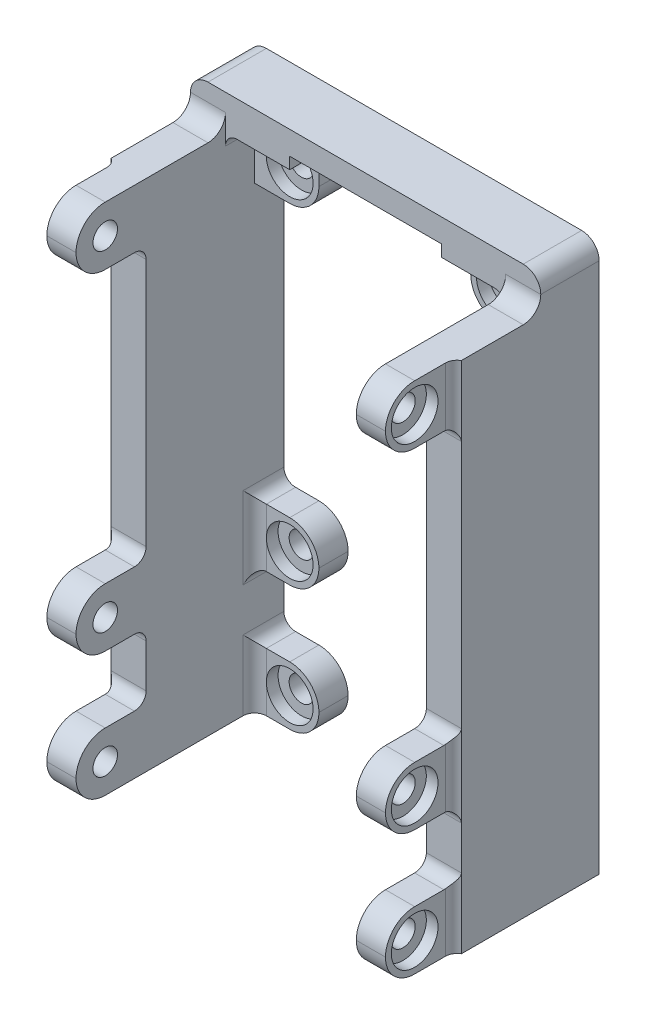
SolidWorks part; units mm, degrees
material "Esun Hard Tough Resin"
ref_plane "Front Plane" through (0, 0, 0) normal (0, 0, 1) x (1, 0, 0)
ref_plane "Top Plane" through (0, 0, 0) normal (0, 1, 0) x (1, 0, 0)
ref_plane "Right Plane" through (0, 0, 0) normal (1, 0, 0) x (0, 0, -1)
sketch "Sketch1" plane through (0, 0, 0) normal (0, 0, 1) x (1, 0, 0)
  line L1 (-15, -22) -> (15, -22)
  line L2 (-15, -22) -> (-15, 22)
  line L3 (-15, 22) -> (15, 22)
  line L4 (15, -22) -> (15, 22)
  line L5 (-15, -22) -> (15, 22) construction
  line L6 (-15, 22) -> (15, -22) construction
  line L7 (-12, 22) -> (12, 22)
  line L8 (-12, 22) -> (-12, -22)
  line L9 (-12, -22) -> (12, -22)
  line L10 (12, 22) -> (12, -22)
  line L11 (-12, 22) -> (12, -22) construction
  line L12 (-12, -22) -> (12, 22) construction
  point P0 (0, 0)
  point P6 (0, 0)
  dimension "D1" = 30
  dimension "D2" = 44
  dimension "D3" = 24
extrude "Boss-Extrude1" add sketch "Sketch1" along normal blind 11.8 contours L8 L3 L2 L1 | L3 L10 L1 L4
sketch "Sketch2" plane through (0, 0, 0) normal (0, 0, -1) x (-1, 0, 0)
  line L1 (-15, 22) -> (15, 22)
  line L2 (-15, 22) -> (-15, 25)
  line L3 (-15, 25) -> (15, 25)
  line L4 (15, 22) -> (15, 25)
  dimension "D1" = 3
extrude "Boss-Extrude2" add sketch "Sketch2" against normal blind 5
sketch "Sketch3" plane through (0, 0, 11.8) normal (0, 0, 1) x (1, 0, 0)
  line L0 (-12, 22) -> (-12, -22) construction
  line L1 (-12, 22) -> (-14.5, 22)
  line L2 (-12, 22) -> (-12, 17)
  line L3 (-12, 17) -> (-14.5, 17)
  line L4 (-14.5, 22) -> (-14.5, 17)
  line L5 (-12, -6.3) -> (-14.5, -6.3)
  line L6 (-12, -6.3) -> (-12, -11.3)
  line L7 (-12, -11.3) -> (-14.5, -11.3)
  line L8 (-14.5, -6.3) -> (-14.5, -11.3)
  line L9 (0, -1000) -> (0, 49000) construction
  line L10 (-12, -17) -> (-14.5, -17)
  line L11 (-12, -17) -> (-12, -22)
  line L12 (-12, -22) -> (-14.5, -22)
  line L13 (-14.5, -17) -> (-14.5, -22)
  line L14 (12, -22) -> (14.5, -22)
  line L15 (14.5, -17) -> (14.5, -22)
  line L16 (12, -17) -> (14.5, -17)
  line L17 (12, -17) -> (12, -22)
  line L18 (12, -11.3) -> (14.5, -11.3)
  line L19 (14.5, -6.3) -> (14.5, -11.3)
  line L20 (12, -6.3) -> (14.5, -6.3)
  line L21 (12, -6.3) -> (12, -11.3)
  line L22 (12, 17) -> (14.5, 17)
  line L23 (14.5, 22) -> (14.5, 17)
  line L24 (12, 22) -> (14.5, 22)
  line L25 (12, 22) -> (12, 17)
  point P15 (-14.5, 19.5)
  point P16 (-14.5, -8.8)
  point P17 (-14.5, -19.5)
  dimension "D1" = 2.5
  dimension "D2" = 2.5
  dimension "D3" = 2.5
  dimension "D4" = 5
  dimension "D5" = 5
  dimension "D6" = 5
  dimension "D7" = 28.3
  dimension "D8" = 10.7
extrude "Boss-Extrude3" add sketch "Sketch3" along normal blind 6
sketch "Sketch4" plane through (-14.5, 0, 0) normal (-1, 0, 0) x (0, 0, 1)
  line L0 (17.8, 22) -> (17.8, 17) construction
  line L2 (17.8, -6.3) -> (17.8, -11.3) construction
  line L4 (17.8, -17) -> (17.8, -22) construction
  circle A0 centre (15.3, 19.5) radius 1.05
  circle A1 centre (15.3, -8.8) radius 1.05
  circle A2 centre (15.3, -19.5) radius 1.05
  point P5 (17.8, 19.5)
  point P12 (17.8, -8.8)
  point P20 (17.8, -19.5)
  dimension "D1" = 2.1
  dimension "D2" = 2.1
  dimension "D3" = 2.1
  dimension "D4" = 2.5
extrude "Cut-Extrude1" cut sketch "Sketch4" against normal through all both
sketch "Sketch5" plane through (0, 0, 0) normal (0, 0, -1) x (-1, 0, 0)
  line L0 (-12, 22) -> (-12, 17) construction
  line L1 (-12, -6.3) -> (-12, -11.3) construction
  line L2 (-12, -17) -> (-12, -22) construction
  line L3 (12, -22) -> (12, -17) construction
  line L4 (12, -11.3) -> (12, -6.3) construction
  line L5 (12, 17) -> (12, 22) construction
  line L6 (-12, 22) -> (-12, 17) construction
  line L7 (-12, -6.3) -> (-12, -11.3) construction
  line L8 (-12, -17) -> (-12, -22) construction
  line L9 (12, -22) -> (12, -17) construction
  line L10 (12, -11.3) -> (12, -6.3) construction
  line L11 (12, 17) -> (12, 22) construction
  line L12 (0, -1000) -> (0, 49000) construction
  line L13 (-12, 22) -> (-6.5, 22)
  line L14 (-12, 22) -> (-12, 17)
  line L15 (-12, 17) -> (-6.5, 17)
  line L16 (-6.5, 22) -> (-6.5, 17)
  line L17 (12, 22) -> (6.5, 22)
  line L18 (12, 22) -> (12, 17)
  line L19 (12, 17) -> (6.5, 17)
  line L20 (6.5, 22) -> (6.5, 17)
  line L21 (-12, -6.3) -> (-6.5, -6.3)
  line L22 (-12, -6.3) -> (-12, -11.3)
  line L23 (-12, -11.3) -> (-6.5, -11.3)
  line L24 (-6.5, -6.3) -> (-6.5, -11.3)
  line L25 (-12, -17) -> (-6.5, -17)
  line L26 (-12, -17) -> (-12, -22)
  line L27 (-12, -22) -> (-6.5, -22)
  line L28 (-6.5, -17) -> (-6.5, -22)
  line L29 (12, -6.3) -> (6.5, -6.3)
  line L30 (12, -6.3) -> (12, -11.3)
  line L31 (12, -11.3) -> (6.5, -11.3)
  line L32 (6.5, -6.3) -> (6.5, -11.3)
  line L33 (12, -17) -> (6.5, -17)
  line L34 (12, -17) -> (12, -22)
  line L35 (12, -22) -> (6.5, -22)
  line L36 (6.5, -17) -> (6.5, -22)
  circle A0 centre (-9, 19.5) radius 1.05
  circle A1 centre (-9, -8.8) radius 1.05
  circle A2 centre (-9, -19.5) radius 1.05
  circle A3 centre (9, -19.5) radius 1.05
  circle A4 centre (9, -8.8) radius 1.05
  circle A5 centre (9, 19.5) radius 1.05
  point P35 (-6.5, -19.5)
  point P37 (-6.5, -8.8)
  point P39 (-6.5, 19.5)
  dimension "D7" = 2.1
  dimension "D8" = 2.1
  dimension "D9" = 2.1
  dimension "D1" = 5.5
  dimension "D2" = 5.5
  dimension "D3" = 5.5
  dimension "D4" = 5.5
  dimension "D5" = 5.5
  dimension "D6" = 5.5
  dimension "D10" = 2.5
extrude "Boss-Extrude4" add sketch "Sketch5" against normal blind 2.5
fillet "Fillet1" radius 2.5 10 edges at (6.5, -17, 1.25) (6.5, -22, 1.25) (6.5, -6.3, 1.25) (6.5, -11.3, 1.25) (-6.5, -22, 1.25) (-6.5, -17, 1.25) (-6.5, -11.3, 1.25) (-6.5, -6.3, 1.25) (-6.5, 17, 1.25) (6.5, 17, 1.25)
fillet "Fillet2" radius 2.5 12 edges at (13.25, -6.3, 17.8) (13.25, -11.3, 17.8) (13.25, -17, 17.8) (13.25, -22, 17.8) (-13.25, -22, 17.8) (-13.25, -17, 17.8) (-13.25, -11.3, 17.8) (-13.25, -6.3, 17.8) (13.25, 22, 17.8) (13.25, 17, 17.8) (-13.25, 17, 17.8) (-13.25, 22, 17.8)
fillet "Fillet3" radius 1.5 3 edges at (15, 25, 2.5) (-15, 25, 2.5) (-13.5, 22, 5)
sketch "Sketch8" plane through (-14.5, 0, 0) normal (-1, 0, 0) x (0, 0, 1)
  circle A0 centre (15.3, 19.5) radius 2
  circle A1 centre (15.3, -8.8) radius 2
  circle A2 centre (15.3, -19.5) radius 2
  dimension "D1" = 4
  dimension "D2" = 4
  dimension "D3" = 4
extrude "Cut-Extrude2" cut sketch "Sketch8" against normal blind 1
sketch "Sketch9" plane through (0, 0, 2.5) normal (0, 0, 1) x (1, 0, 0)
  circle A0 centre (-9, 19.5) radius 2
  circle A1 centre (-9, -8.8) radius 2
  circle A2 centre (-9, -19.5) radius 2
  dimension "D1" = 4
  dimension "D2" = 4
  dimension "D3" = 4
extrude "Cut-Extrude3" cut sketch "Sketch9" against normal blind 1
mirror "Mirror1" about plane through (0, 0, 0) normal (1, 0, 0) of "Cut-Extrude3", "Cut-Extrude2"
fillet "Fillet4" radius 1 26 edges at (12, 22, 3.75) (-12, 22, 3.75) (12, -6.3, 1.25) (12, -17, 1.25) (12, -8.8, 2.5) (12, -11.3, 1.25) (12, -19.5, 2.5) (-12, -11.3, 1.25) (-12, -19.5, 2.5) (-12, -17, 1.25) (-12, -8.8, 2.5) (-12, -6.3, 1.25) (-14.5, 19.5, 11.8) (-14.5, -8.8, 11.8) (-13.25, -6.3, 11.8) (-14.5, -19.5, 11.8) (-13.25, -17, 11.8) (13.25, -17, 11.8) (13.25, -6.3, 11.8) (-13.25, 17, 11.8) (-13.25, -11.3, 11.8) (14.5, -19.5, 11.8) (14.5, -8.8, 11.8) (13.25, -11.3, 11.8) (13.25, 17, 11.8) (14.5, 19.5, 11.8)
sketch "Sketch10" plane through (0, 0, 0) normal (0, 0, -1) x (-1, 0, 0)
  line L1 (-6.5, 22) -> (6.5, 22)
  line L2 (-6.5, 22) -> (-6.5, 23)
  line L3 (-6.5, 23) -> (6.5, 23)
  line L4 (6.5, 22) -> (6.5, 23)
  dimension "D1" = 1
extrude "Cut-Extrude4" cut sketch "Sketch10" against normal through all
equation "\"D2@Sketch3\"=\"D1@Sketch3\""
equation "\"D3@Sketch3\"=\"D1@Sketch3\""
equation "\"D5@Sketch3\"=\"D4@Sketch3\""
equation "\"D6@Sketch3\"=\"D4@Sketch3\""
equation "\"D2@Sketch4\"=\"D1@Sketch4\""
equation "\"D3@Sketch4\"=\"D1@Sketch4\""
equation "\"D2@Sketch5\"=\"D1@Sketch5\""
equation "\"D3@Sketch5\"=\"D1@Sketch5\""
equation "\"D4@Sketch5\"=\"D1@Sketch5\""
equation "\"D5@Sketch5\"=\"D1@Sketch5\""
equation "\"D6@Sketch5\"=\"D1@Sketch5\""
equation "\"D8@Sketch5\"=\"D7@Sketch5\""
equation "\"D9@Sketch5\"=\"D7@Sketch5\""
equation "\"D2@Sketch8\"=\"D1@Sketch8\""
equation "\"D3@Sketch8\"=\"D1@Sketch8\""
equation "\"D2@Sketch9\"=\"D1@Sketch9\""
equation "\"D3@Sketch9\"=\"D1@Sketch9\""
